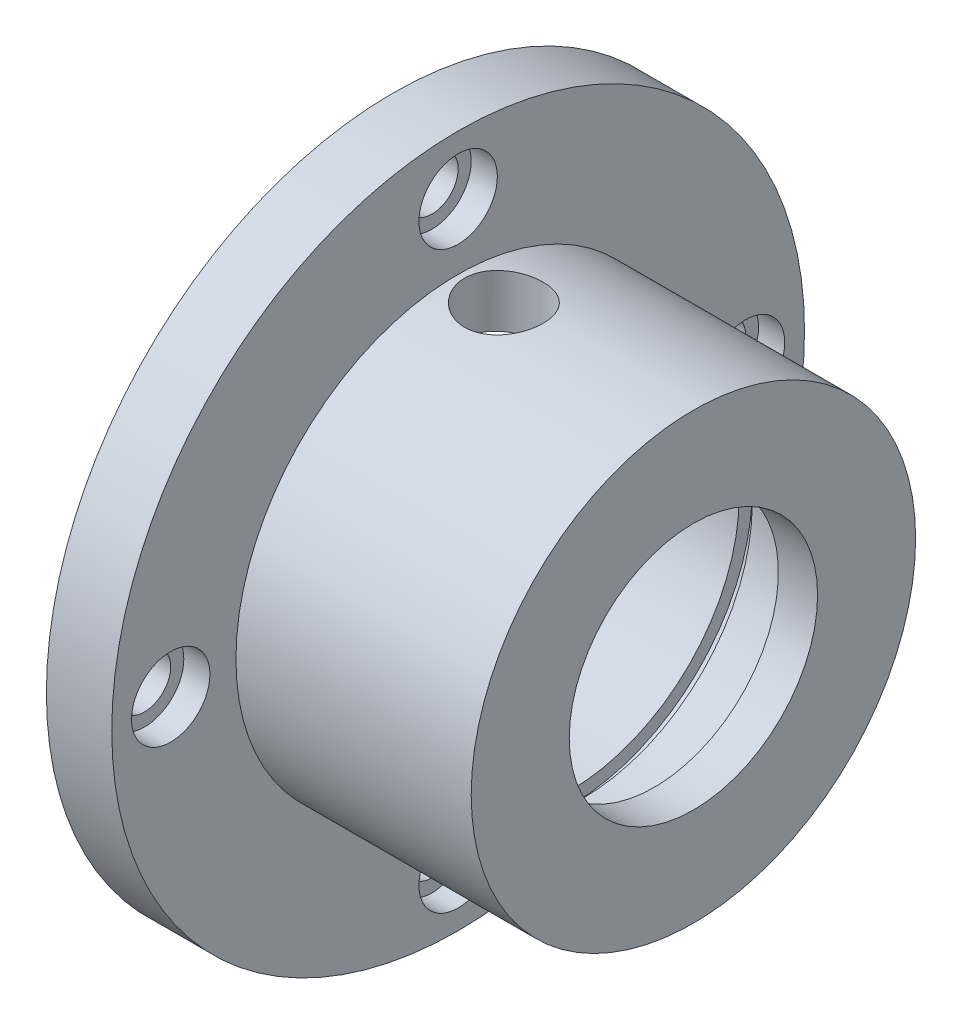
SolidWorks part; units mm, degrees
ref_plane "Front Plane" through (0, 0, 0) normal (0, 0, 1) x (1, 0, 0)
ref_plane "Top Plane" through (0, 0, 0) normal (0, 1, 0) x (1, 0, 0)
ref_plane "Right Plane" through (0, 0, 0) normal (1, 0, 0) x (0, 0, -1)
sketch "Sketch1" plane through (0, 0, 0) normal (1, 0, 0) x (0, 0, -1)
  circle A0 centre (0, 0) radius 26.5
  circle A2 centre (0, -21.9877) radius 2
  circle A3 centre (-21.9877, 0) radius 2
  circle A4 centre (0, 21.9877) radius 2
  circle A5 centre (21.9877, 0) radius 2
  point P14 (0, 0)
  dimension "D1" = 53
  dimension "D2" = 4
  dimension "D3" = 4
extrude "Boss-Extrude1" add sketch "Sketch1" along normal mid plane 23
sketch "Sketch2" plane through (11.5, 0, 0) normal (1, 0, 0) x (0, 0, -1)
  circle A0 centre (0, 0) radius 17
  circle A1 centre (0, 0) radius 26.5
  circle M3 centre (0, 21.9877) radius 2
  circle M4 centre (0, -21.9877) radius 2
  circle M5 centre (0, 0) radius 26.5
  circle M6 centre (-21.9877, 0) radius 2
  circle M7 centre (21.9877, 0) radius 2
  dimension "D1" = 53
  dimension "D3" = 34
extrude "Cut-Extrude1" cut sketch "Sketch2" against normal blind 18 contours A0 M5 M4 M6 M7 M3 region at (11.5, 0, 25.7505)
sketch "Sketch3" plane through (-11.5, 0, 0) normal (-1, 0, 0) x (0, 0, 1)
  circle A0 centre (0, 0) radius 13
  dimension "D1" = 26
extrude "Cut-Extrude2" cut sketch "Sketch3" against normal blind 20
sketch "Sketch4" plane through (8.5, 0, 0) normal (-1, 0, 0) x (0, 0, 1)
  circle A0 centre (0, 0) radius 9.5
  dimension "D1" = 19
extrude "Cut-Extrude3" cut sketch "Sketch4" against normal blind 20
ref_plane "Plane1" through (2.5, 0, 0) normal (-1, 0, 0) x (0, 0, 1)
sketch "Sketch5" plane through (2.5, 0, 0) normal (-1, 0, 0) x (0, 0, 1)
  circle A0 centre (0, 0) radius 14
  dimension "D1" = 28
extrude "Cut-Extrude4" cut sketch "Sketch5" against normal mid plane 1
ref_axis "Axis1" through (26.7383, 0, 0) along (-1, 0, 0)
sketch "Sketch6" plane through (0, 0, 0) normal (0, 1, 0) x (1, 0, 0)
  line L0 (26.7383, 0) -> (-32.37, 0) construction
  line L1 (11.5, -17) -> (11.5, 17) construction
  circle A0 centre (-3, 0) radius 3
  dimension "D1" = 14.5
extrude "Cut-Extrude5" cut sketch "Sketch6" along normal blind 33
ref_plane "Plane3" through (0, 17, 0) normal (0, 1, 0) x (1, 0, 0)
sketch "Sketch8" plane through (0, 17, 0) normal (0, 1, 0) x (1, 0, 0)
  line L1 (0.1411, -6) -> (-6.1411, -6)
  line L2 (0.1411, -6) -> (0.1411, 6)
  line L3 (0.1411, 6) -> (-6.1411, 6)
  line L4 (-6.1411, -6) -> (-6.1411, 6)
  line L5 (0.1411, -6) -> (-6.1411, 6) construction
  line L6 (0.1411, 6) -> (-6.1411, -6) construction
  point P0 (-3, 0)
  dimension "D1" = 12
extrude "Cut-Extrude6" [suppressed] cut sketch "Sketch8" against normal blind 1
sketch "Sketch9" plane through (-6.5, 0, 0) normal (1, 0, 0) x (0, 0, -1)
  circle A0 centre (0, 21.9877) radius 3
  circle A1 centre (21.9877, 0) radius 3
  circle A2 centre (0, -21.9877) radius 3
  circle A3 centre (-21.9877, 0) radius 3
  point P12 (0, 0)
  dimension "D1" = 4
extrude "Cut-Extrude7" cut sketch "Sketch9" against normal blind 2
